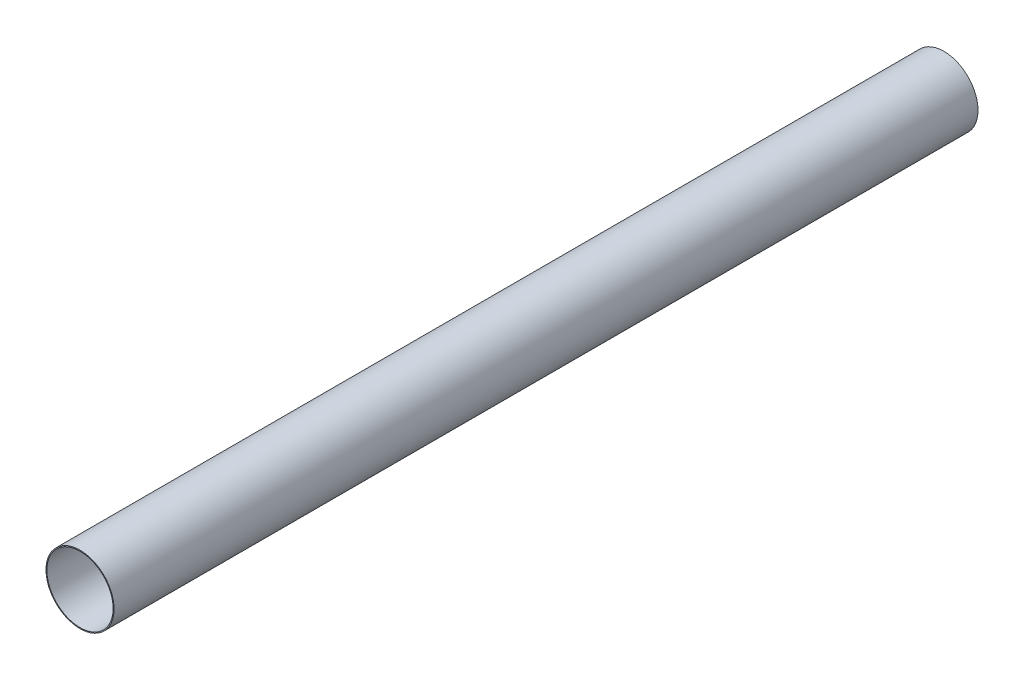
SolidWorks part; units mm, degrees
material "Fibra di Carbonio"
ref_plane "Front Plane" through (0, 0, 0) normal (0, 0, 1) x (1, 0, 0)
ref_plane "Top Plane" through (0, 0, 0) normal (0, 1, 0) x (1, 0, 0)
ref_plane "Right Plane" through (0, 0, 0) normal (1, 0, 0) x (0, 0, -1)
sketch "Sketch1" plane through (0, 0, 0) normal (0, 0, 1) x (1, 0, 0)
  circle A0 centre (0, 0) radius 73
  circle A1 centre (0, 0) radius 75
  dimension "D1" = 150
  dimension "D2" = 2
extrude "Boss-Extrude1" add sketch "Sketch1" along normal offset from surface (1904.3992 mm away) 20
